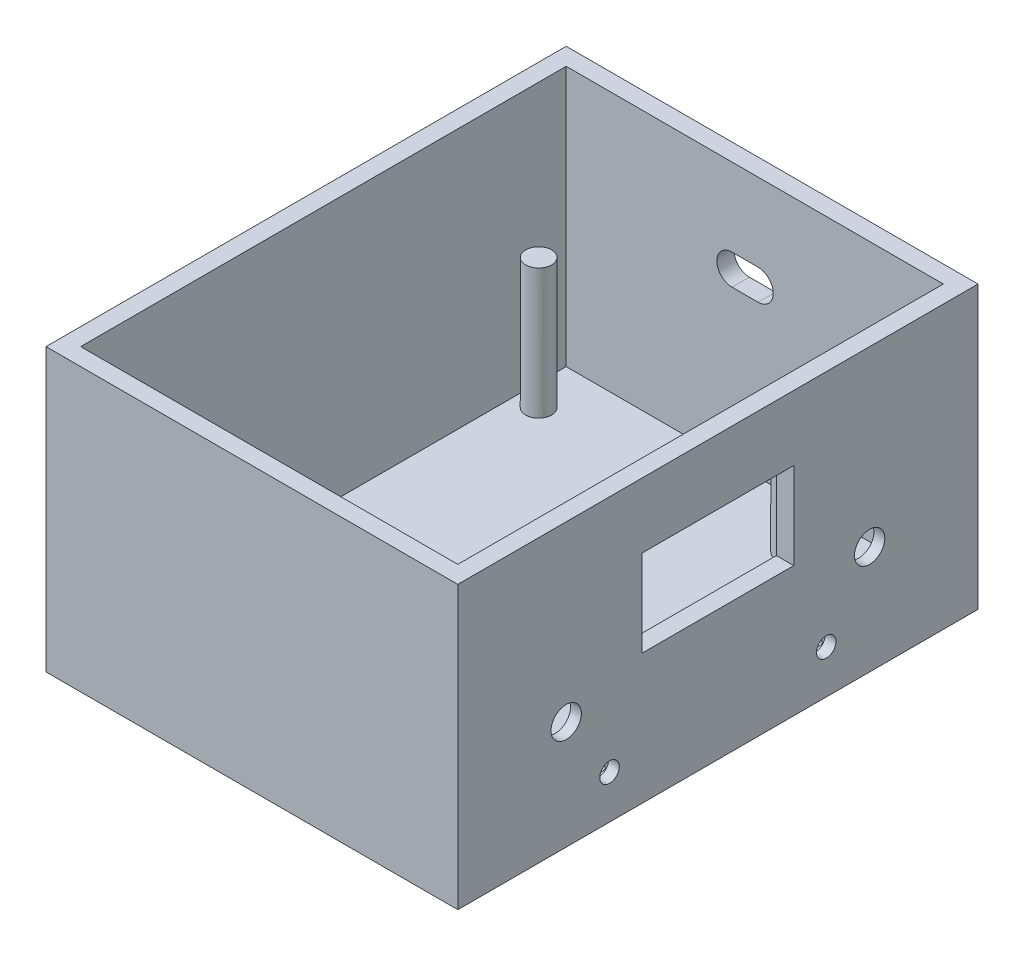
SolidWorks part; units mm, degrees
ref_plane "Front Plane" through (0, 0, 0) normal (0, 0, 1) x (1, 0, 0)
ref_plane "Top Plane" through (0, 0, 0) normal (0, 1, 0) x (1, 0, 0)
ref_plane "Right Plane" through (0, 0, 0) normal (1, 0, 0) x (0, 0, -1)
sketch "Sketch1" plane through (0, 0, 0) normal (0, 1, 0) x (1, 0, 0)
  line L1 (-47.5, -60) -> (47.5, -60)
  line L2 (-47.5, -60) -> (-47.5, 60)
  line L3 (-47.5, 60) -> (47.5, 60)
  line L4 (47.5, -60) -> (47.5, 60)
  line L5 (-47.5, -60) -> (47.5, 60) construction
  line L6 (-47.5, 60) -> (47.5, -60) construction
  point P0 (0, 0)
  dimension "D1" = 120
  dimension "D2" = 95
extrude "base dimensions" add sketch "Sketch1" along normal blind 5
sketch "Sketch2" plane through (0, 5, 0) normal (0, 1, 0) x (1, 0, 0)
  line L0 (47.5, -60) -> (47.5, 60) construction
  line L1 (-47.5, -60) -> (47.5, -60) construction
  line L2 (-47.5, 60) -> (-47.5, -60) construction
  line L3 (47.5, 60) -> (-47.5, 60) construction
  line L4 (47.5, -60) -> (47.5, 60)
  line L5 (-47.5, -60) -> (47.5, -60)
  line L6 (-47.5, 60) -> (-47.5, -60)
  line L7 (47.5, 60) -> (-47.5, 60)
  line L9 (-43.5, -56) -> (43.5, -56)
  line L10 (-43.5, -56) -> (-43.5, 56)
  line L11 (-43.5, 56) -> (43.5, 56)
  line L12 (43.5, -56) -> (43.5, 56)
  line L13 (-43.5, -56) -> (43.5, 56) construction
  line L14 (-43.5, 56) -> (43.5, -56) construction
  point P4 (0, 0)
  dimension "D1" = 4
  dimension "D2" = 4
extrude "wall height and depth" add sketch "Sketch2" along normal blind 60
sketch "Sketch3" plane through (0, 5, 0) normal (0, 1, 0) x (1, 0, 0)
  line L0 (-43.5, 56) -> (-43.5, -56) construction
  line L1 (-43.5, -56) -> (43.5, -56) construction
  circle A0 centre (-38.5, 44.645) radius 3
  circle A1 centre (-38.5, -36) radius 3
  circle A2 centre (32.62, -36) radius 3
  circle A3 centre (19.285, 44.645) radius 3
  dimension "D4" = 6
  dimension "D1" = 57.785
  dimension "D2" = 71.12
  dimension "D3" = 80.645
  dimension "D5" = 5
  dimension "D6" = 20
extrude "support pegs" add sketch "Sketch3" along normal blind 30
sketch "Sketch4" plane through (47.5, 0, 0) normal (1, 0, 0) x (0, 0, -1)
  line L0 (0, 71.0913) -> (0, -6.0913) construction
  line L1 (-17.5, 50) -> (17.5, 50)
  line L2 (-17.5, 50) -> (-17.5, 30)
  line L3 (-17.5, 30) -> (17.5, 30)
  line L4 (17.5, 50) -> (17.5, 30)
  line L5 (-17.5, 50) -> (17.5, 30) construction
  line L6 (-17.5, 30) -> (17.5, 50) construction
  line L7 (52.25, 0) -> (-52.25, 0) construction
  line L8 (-60, 65) -> (60, 65) construction
  circle A0 centre (-35, 25) radius 3.5
  circle A1 centre (-25, 10) radius 2.25
  circle A2 centre (25, 10) radius 2.25
  circle A3 centre (35, 25) radius 3.5
  point P0 (0, 40)
  point P12 (25, 10)
  dimension "D3" = 7
  dimension "D4" = 4.5
  dimension "D1" = 25
  dimension "D2" = 35
  dimension "D5" = 10
  dimension "D6" = 25
  dimension "D7" = 20
  dimension "D8" = 35
  dimension "D9" = 25
extrude "front holes" cut sketch "Sketch4" against normal up to surface (4 mm away) up to face at (43.5, 35, 0)
sketch "Sketch6" plane through (43.5, 0, 0) normal (-1, 0, 0) x (0, 0, 1)
  line L0 (0, -35.75) -> (0, 35.75) construction
  line L1 (-41.75, 31.375) -> (-28.25, 31.375)
  line L2 (-41.75, 31.375) -> (-41.75, 18.625)
  line L3 (-41.75, 18.625) -> (-28.25, 18.625)
  line L4 (-28.25, 31.375) -> (-28.25, 18.625)
  line L5 (-41.75, 31.375) -> (-28.25, 18.625) construction
  line L6 (-41.75, 18.625) -> (-28.25, 31.375) construction
  line L7 (-28, 7) -> (-22, 7)
  line L8 (-28, 7) -> (-28, 13)
  line L9 (-28, 13) -> (-22, 13)
  line L10 (-22, 7) -> (-22, 13)
  line L11 (-28, 7) -> (-22, 13) construction
  line L12 (-28, 13) -> (-22, 7) construction
  line L13 (28, 13) -> (22, 7) construction
  line L14 (28, 7) -> (22, 13) construction
  line L15 (41.75, 18.625) -> (28.25, 31.375) construction
  line L16 (41.75, 31.375) -> (28.25, 18.625) construction
  line L17 (22, 7) -> (22, 13)
  line L18 (28, 13) -> (22, 13)
  line L19 (28, 7) -> (28, 13)
  line L20 (28, 7) -> (22, 7)
  line L21 (28.25, 31.375) -> (28.25, 18.625)
  line L22 (41.75, 18.625) -> (28.25, 18.625)
  line L23 (41.75, 31.375) -> (41.75, 18.625)
  line L24 (41.75, 31.375) -> (28.25, 31.375)
  point P0 (-35, 25)
  point P6 (-25, 10)
  point P22 (25, 10)
  point P23 (35, 25)
  dimension "D1" = 13.5
  dimension "D2" = 12.75
  dimension "D3" = 6
extrude "en and b inlay" cut sketch "Sketch6" against normal blind 1.5
sketch "screen mounting layout" plane through (43.5, 0, 0) normal (-1, 0, 0) x (0, 0, 1)
  line L0 (0, -35.75) -> (0, 35.75) construction
  line L8 (-15.265, 24.85) -> (15.265, 24.85) construction
  line L9 (-15.265, 24.85) -> (-15.265, 53.46) construction
  line L10 (-15.265, 53.46) -> (15.265, 53.46) construction
  line L11 (15.265, 24.85) -> (15.265, 53.46) construction
  line L12 (-15.265, 24.85) -> (15.265, 53.46) construction
  line L13 (-15.265, 53.46) -> (15.265, 24.85) construction
  line L14 (-15.265, 23.3) -> (15.265, 23.3) construction
  line L15 (17.5, 30) -> (-17.5, 30) construction
  circle A0 centre (-15.265, 53.46) radius 1.55 construction
  circle A1 centre (-15.265, 24.85) radius 1.55 construction
  circle A2 centre (15.265, 24.85) radius 1.55 construction
  circle A3 centre (15.265, 53.46) radius 1.55 construction
  point P8 (0, 39.155)
  dimension "D3" = 3.1
  dimension "D4" = 3.1
  dimension "D1" = 30.53
  dimension "D2" = 28.61
  dimension "D5" = 6.7
sketch "Sketch9" plane through (0, 0, -56) normal (0, 0, 1) x (1, 0, 0)
  line L0 (-5.236, 43.5) -> (0.764, 43.5) construction
  line L1 (-5.236, 47) -> (0.764, 47)
  line L2 (-5.236, 40) -> (0.764, 40)
  line L3 (43.5, 5) -> (-43.5, 5) construction
  line L4 (-43.5, 65) -> (-43.5, 5) construction
  arc A0 (-5.236, 47) -> (-5.236, 40) centre (-5.236, 43.5) ccw
  arc A1 (0.764, 40) -> (0.764, 47) centre (0.764, 43.5) ccw
  point P2 (-2.236, 43.5)
  dimension "D2" = 3.5
  dimension "D1" = 6
  dimension "D3" = 35
  dimension "D4" = 41.264
extrude "usb slot" cut sketch "Sketch9" against normal through all
